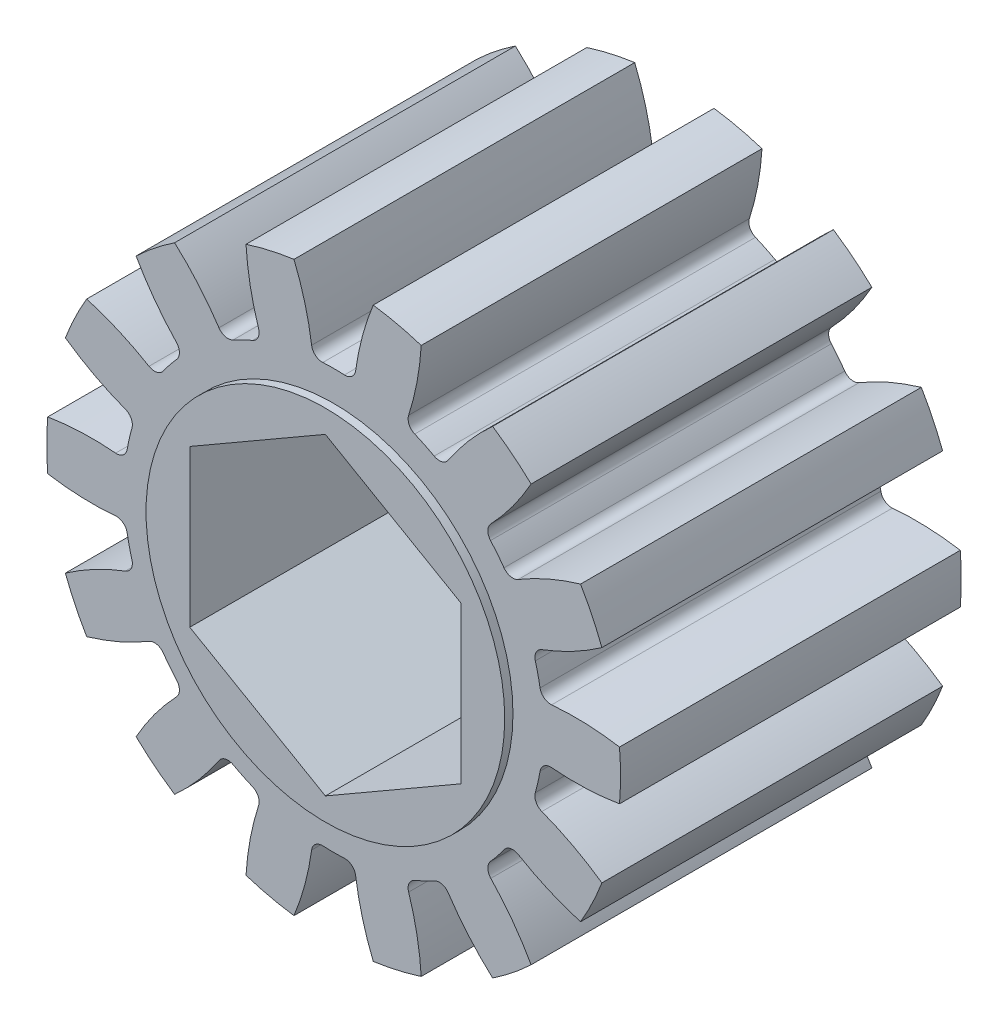
SolidWorks part; units mm, degrees
material "7075-T6 (SN)"
ref_plane "Alzado" through (0, 0, 0) normal (0, 0, 1) x (1, 0, 0)
ref_plane "Planta" through (0, 0, 0) normal (0, 1, 0) x (1, 0, 0)
ref_plane "Vista lateral" through (0, 0, 0) normal (1, 0, 0) x (0, 0, -1)
sketch "Croquis1" plane through (0, 0, 0) normal (0, 0, 1) x (1, 0, 0)
  circle A0 centre (0, 0) radius 8.89 construction
  circle A1 centre (0, 0) radius 10.16
  dimension "D" = 17.78
  dimension "OD" = 20.32
extrude "Saliente-Extruir1" add sketch "Croquis1" along normal mid plane 12.065
sketch "Croquis2" plane through (0, 0, 0) normal (0, 0, 1) x (1, 0, 0)
  line L0 (0, 0) -> (0, 10.16) construction
  line L1 (0, 0) -> (4.4083, 9.1538) construction
  line L2 (0, 0) -> (2.2608, 9.9053) construction
  line L3 (-0.737, 7.3839) -> (0, 0) construction
  line L4 (-0.9954, 8.8341) -> (0.9954, 8.8341) construction
  line L5 (0.9954, 8.8341) -> (2.9362, 8.3911) construction
  line L6 (-1.3161, 10.0744) -> (0, 4.9853) construction
  circle A0 centre (0, 0) radius 10.16 construction
  arc A2 (0.737, 7.3839) -> (-0.737, 7.3839) centre (0, 0) ccw
  circle A5 centre (0, 0) radius 8.89 construction
  arc A6 (-1.4032, 10.0626) -> (-0.737, 7.3839) centre (-10.2899, 6.4304) cw
  arc A7 (1.4032, 10.0626) -> (0.737, 7.3839) centre (10.2899, 6.4304) ccw
  arc A8 (1.4032, 10.0626) -> (-1.4032, 10.0626) centre (0, 0) ccw
  dimension "D1" = 25.714
  dimension "D2" = 12.857
  dimension "B" = 1.4694
  dimension "Pressure Angle" = 14.5
extrude "Cortar-Extruir1" cut sketch "Croquis2" against normal through all both and the other way through all
fillet "Redondeo1" radius 0.381 2 edges at (0.737, 7.3839, 0) (-0.737, 7.3839, 0)
pattern_circular "MatrizC1" count 14 over 360 about axis through (0, 0, 6.0325) along (0, 0, -1) of "Cortar-Extruir1", "Redondeo1"
sketch "Croquis3" plane through (0, 0, 0) normal (0, 0, 1) x (1, 0, 0)
  circle A0 centre (0, 0) radius 6.35
  dimension "sp" = 12.7
extrude "Saliente-Extruir2" add sketch "Croquis3" along normal mid plane 12.6492
sketch "Croquis4" plane through (0, 0, 0) normal (0, 0, 1) x (1, 0, 0)
  line L1 (0, 5.5433) -> (-4.8006, 2.7716)
  line L2 (-4.8006, 2.7716) -> (-4.8006, -2.7716)
  line L3 (-4.8006, -2.7716) -> (0, -5.5433)
  line L4 (0, -5.5433) -> (4.8006, -2.7716)
  line L5 (4.8006, -2.7716) -> (4.8006, 2.7716)
  line L6 (4.8006, 2.7716) -> (0, 5.5433)
  circle A0 centre (0, 0) radius 4.8006 construction
  dimension "D1" = 9.6012
  dimension "D2" = 12.857
extrude "Cortar-Extruir2" cut sketch "Croquis4" against normal through all both and the other way through all
equation "\"Number of teeth\"=14"
equation "\"Diametral Pitch\"= 20"
equation "\"Pressure Angle\"= 14.5"
equation "\"D@Croquis1\"=\"Number of teeth\"/\"Diametral Pitch\""
equation "\"OD@Croquis1\"=(\"Number of teeth\"+2) /\"Diametral Pitch\""
equation "\"D2@Croquis2\"=(360 / \"Number of teeth\")/ 2."
equation "\"D1@Croquis2\"=360 / \"Number of teeth\""
equation "\"B@Croquis2\"=1.157 / \"Diametral Pitch\""
equation "\"Pressure Angle@Croquis2\" = \"Pressure Angle\""
equation "\"D1@Redondeo1\"=(pi / \"Diametral Pitch\") * .0955"
equation "\"D1@MatrizC1\"=\"Number of teeth\""
equation "\"Tt@Saliente-Extruir1\"=if( \"Number of teeth\"=>30,0.375,0.475)"
